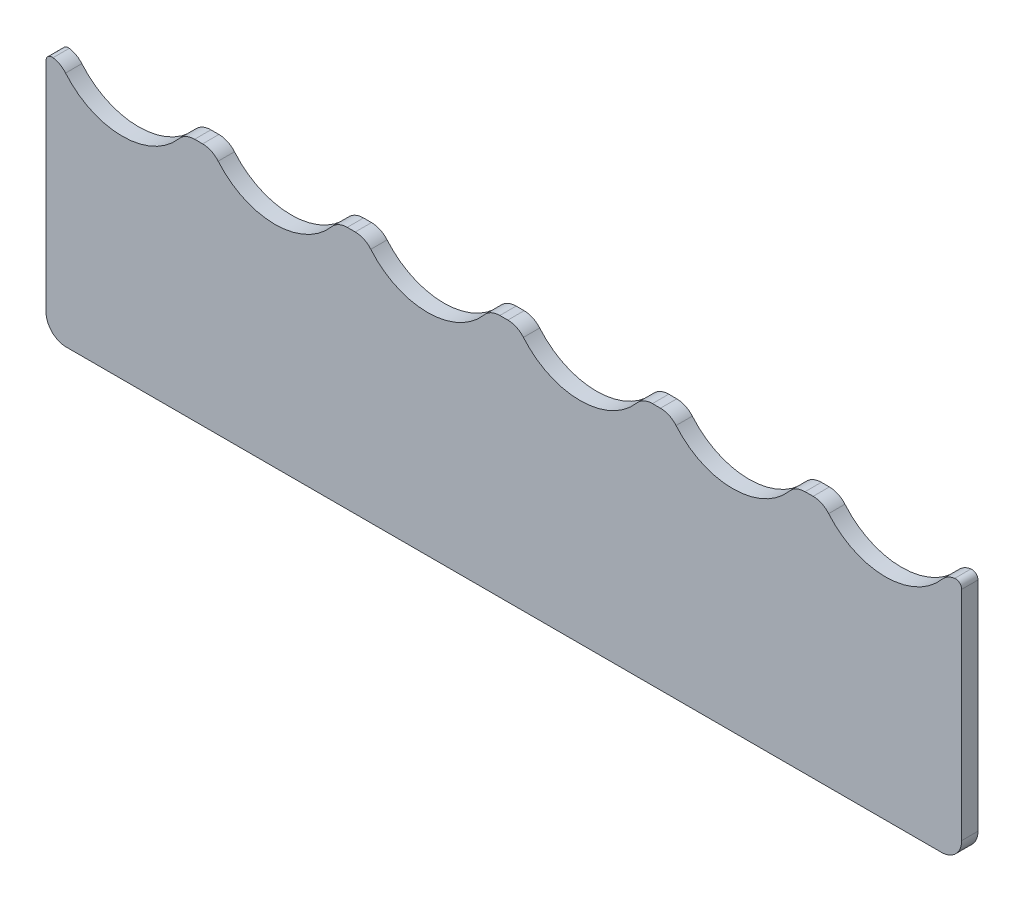
SolidWorks part; units mm, degrees
ref_plane "Plan de face" through (0, 0, 0) normal (0, 0, 1) x (1, 0, 0)
ref_plane "Plan de dessus" through (0, 0, 0) normal (0, 1, 0) x (1, 0, 0)
ref_plane "Plan de droite" through (0, 0, 0) normal (1, 0, 0) x (0, 0, -1)
sketch "Esquisse1" plane through (0, 0, 0) normal (0, 0, 1) x (1, 0, 0)
  line L0 (225, 0) -> (225, 120) construction
  line L1 (0, 0) -> (450, 0)
  line L2 (0, 0) -> (0, 120)
  line L3 (0, 120) -> (450, 120)
  line L4 (450, 0) -> (450, 120)
  dimension "D1" = 450
  dimension "D2" = 120
extrude "Boss.-Extru.1" add sketch "Esquisse1" along normal blind 8
sketch "Esquisse2" plane through (0, 0, 8) normal (0, 0, 1) x (1, 0, 0)
  line L0 (225, 0) -> (225, 120) construction
  line L1 (0, 0) -> (450, 0) construction
  line L2 (450, 120) -> (0, 120) construction
  line L3 (187.5, 140) -> (187.5, 87.5884) construction
  line L4 (187.5, 87.5884) -> (225, 87.5884) construction
  line L5 (37.5, 140) -> (112.5, 140) construction
  line L6 (112.5, 140) -> (187.5, 140) construction
  line L7 (337.5, 140) -> (262.5, 140) construction
  line L8 (412.5, 140) -> (337.5, 140) construction
  circle A0 centre (187.5, 140) radius 36.5
  circle A1 centre (112.5, 140) radius 36.5
  circle A2 centre (37.5, 140) radius 36.5
  circle A3 centre (412.5, 140) radius 36.5
  circle A4 centre (337.5, 140) radius 36.5
  circle A5 centre (262.5, 140) radius 36.5
  dimension "D1" = 73
  dimension "D2" = 75
  dimension "D3" = 75
  dimension "D5" = 20
  dimension "D4" = 37.5
extrude "Enlèv. mat.-Extru.1" cut sketch "Esquisse2" against normal through all both and the other way through all
fillet "Congé1" radius 10 14 edges at (6.9672, 120, 4) (443.0328, 120, 4) (381.9672, 120, 4) (368.0328, 120, 4) (306.9672, 120, 4) (293.0328, 120, 4) (231.9672, 120, 4) (218.0328, 120, 4) (156.9672, 120, 4) (143.0328, 120, 4) (81.9672, 120, 4) (68.0328, 120, 4) (450, 0, 4) (0, 0, 4)
fillet "Congé2" radius 3 2 edges at (450, 120, 4) (0, 120, 4)
